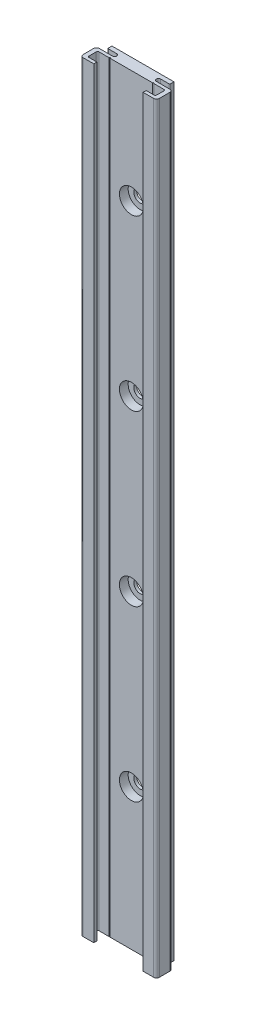
SolidWorks part; units mm, degrees
ref_plane "Front Plane" through (0, 0, 0) normal (0, 0, 1) x (1, 0, 0)
ref_plane "Top Plane" through (0, 0, 0) normal (0, 1, 0) x (1, 0, 0)
ref_plane "Right Plane" through (0, 0, 0) normal (1, 0, 0) x (0, 0, -1)
ref_plane "Plane1" through (0, 300, 0) normal (0, 1, 0) x (1, 0, 0)
sketch "Sketch1" plane through (0, 300, 0) normal (0, 1, 0) x (1, 0, 0)
  line L0 (-13.5, -3) -> (-13.5, -8.7)
  line L1 (-13.5, -8.7) -> (13.5, -8.7)
  line L2 (13.5, -8.7) -> (13.5, -3)
  line L3 (13.5, -3) -> (7.8, -3)
  line L4 (7.8, -1.5) -> (11, -1.5)
  line L5 (11, -1.5) -> (11, 0)
  line L6 (11, 0) -> (-11, 0)
  line L7 (-11, 0) -> (-11, -1.5)
  line L8 (-11, -1.5) -> (-7.8, -1.5)
  line L9 (-7.8, -3) -> (-13.5, -3)
  arc A0 (7.8, -3) -> (7.8, -1.5) centre (7.8, -2.25) cw
  arc A1 (-7.8, -1.5) -> (-7.8, -3) centre (-7.8, -2.25) cw
extrude "Boss-Extrude1" add sketch "Sketch1" against normal blind 270
sketch "Sketch2" plane through (0, 30, 0) normal (0, -1, 0) x (1, 0, 0)
  line L0 (8.75, 8.7) -> (-8.75, 8.7)
  line L1 (-8.75, 8.7) -> (-8.75, 7.6)
  line L2 (-8.75, 7.6) -> (-12, 7.6)
  line L3 (-12, 7.6) -> (-12, 4.1)
  line L4 (-12, 4.1) -> (12, 4.1)
  line L5 (12, 4.1) -> (12, 7.6)
  line L6 (12, 7.6) -> (8.75, 7.6)
  line L7 (8.75, 7.6) -> (8.75, 8.7)
extrude "Cut-Extrude1" cut sketch "Sketch2" against normal through all
hole_wizard "Ø0.4 (0.4) Diameter Hole1" positions "Sketch4" profile "Sketch3" hole size "Ø0.4" standard "ANSI Metric"
sketch "Sketch4" plane through (0, 300, 0) normal (0, 1, 0) x (1, 0, 0)
  point P0 (-7.75, -4.1)
  point P1 (7.75, -4.1)
sketch "Sketch3" plane through (-7.75, 300, 4.1) normal (1, 0, 0) x (0, 0, 1)
  line L0 (0, 0) -> (0, 270)
  line L1 (0, 270) -> (0.2, 270)
  line L2 (0.2, 270) -> (0.2, 0)
  line L5 (0.2, 0) -> (0, 0)
  line L11 (0, -6.35) -> (0, 107.95) construction
  dimension "Thru Hole Dia." = 0.4
  dimension "Thru Hole Depth" = 270
hole_wizard "CBORE for M4 Hex Head Machine Screw1" positions "Sketch6" profile "Sketch5" counterbore size "M4" standard "ANSI Metric"
sketch "Sketch6" plane through (0, 0, 4.1) normal (0, 0, 1) x (1, 0, 0)
  point P0 (0, 260)
  point P1 (0, 200)
  point P2 (0, 140)
  point P3 (0, 80)
  point P4 (0, 20)
sketch "Sketch5" plane through (0, 260, 4.1) normal (1, 0, 0) x (0, -1, 0)
  line L0 (0, 0) -> (0, 4.1)
  line L1 (0, 4.1) -> (2.25, 4.1)
  line L3 (2.25, 4.1) -> (2.25, 3.1)
  line L4 (2.25, 3.1) -> (4.25, 3.1)
  line L5 (4.25, 3.1) -> (4.25, 0)
  line L7 (4.25, 0) -> (0, 0)
  line L11 (0, -6.35) -> (0, 107.95) construction
  dimension "Thru Hole Dia." = 4.5
  dimension "Thru Hole Depth" = 4.1
  dimension "C'Bore Dia." = 8.5
  dimension "C'Bore Depth" = 3.1
fillet "Fillet1" radius 0.2 2 edges at (11, 165, 1.5) (-11, 165, 1.5) tangent propagation no
fillet "Fillet2" radius 0.5 4 edges at (12, 165, 4.1) (-12, 165, 7.6) (12, 165, 7.6) (-12, 165, 4.1) tangent propagation no
fillet "Fillet3" radius 1 4 edges at (-13.5, 165, 8.7) (-13.5, 165, 3) (13.5, 165, 3) (13.5, 165, 8.7) tangent propagation no
